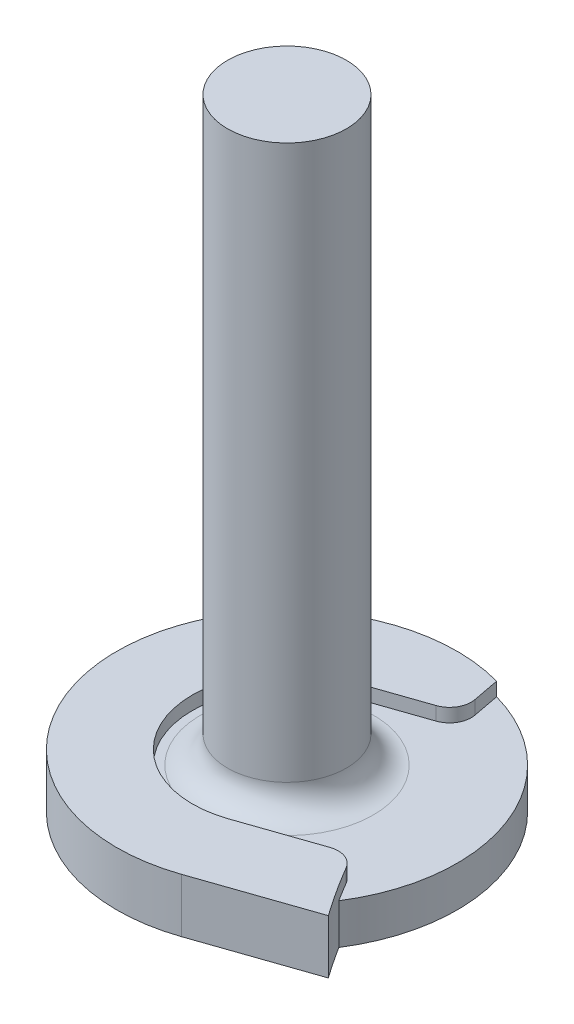
SolidWorks part; units mm, degrees
ref_plane "Alzado" through (0, 0, 0) normal (0, 0, 1) x (1, 0, 0)
ref_plane "Planta" through (0, 0, 0) normal (0, 1, 0) x (1, 0, 0)
ref_plane "Vista lateral" through (0, 0, 0) normal (1, 0, 0) x (0, 0, -1)
sketch "Croquis1" plane through (0, 0, 0) normal (0, 1, 0) x (1, 0, 0)
  line L4 (-28.127, 104.148) -> (-32.1677, 102.7551) construction
  line L5 (-28.127, 104.148) -> (-32.1677, 102.7551)
  arc A6 (-36.2739, 114.6672) -> (-32.1677, 102.7551) centre (-34.2208, 108.7112) ccw construction
  arc A7 (-28.9113, 105.3201) -> (-32.1677, 102.7551) centre (-34.2208, 108.7112) ccw
  arc A8 (-29.334, 106.0147) -> (-28.127, 104.148) centre (-7.0429, 119.104) ccw construction
  arc A9 (-28.9113, 105.3201) -> (-28.127, 104.148) centre (-7.0429, 119.104) ccw
extrude "Saliente-Extruir1" add sketch "Croquis1" along normal blind 1.5 contours A7 region at (-34.147, 0, -108.6415)
sketch "Sketch1" plane through (0, 1.5, 0) normal (0, 1, 0) x (1, 0, 0)
  circle A1 centre (-34.2208, 108.7112) radius 2.2
  dimension "D1" = 4.4
extrude "Boss-Extrude1" add sketch "Sketch1" along normal up to surface (21.5 mm away)
fillet "Fillet1" radius 1 1 edges at (-34.2208, 1.5, -106.5112)
sketch "Sketch2" plane through (0, 1.5, 0) normal (0, 1, 0) x (1, 0, 0)
  line L0 (-28.127, 104.148) -> (-32.1677, 102.7551) construction
  line L1 (-28.127, 104.148) -> (-32.1677, 102.7551)
  line L2 (-30.2846, 106.3659) -> (-33.0802, 105.4022) construction
  line L3 (-30.2846, 106.3659) -> (-33.0802, 105.4022)
  line L4 (-35.3614, 112.0201) -> (-32.8654, 112.8805) construction
  line L5 (-35.3614, 112.0201) -> (-32.8654, 112.8805)
  line L6 (-32.3431, 113.8009) -> (-32.5286, 114.7796)
  arc A0 (-28.9113, 105.3201) -> (-32.1677, 102.7551) centre (-34.2208, 108.7112) ccw construction
  arc A2 (-32.5286, 114.7796) -> (-32.1677, 102.7551) centre (-34.2208, 108.7112) ccw
  arc A4 (-30.9277, 128.9904) -> (-32.3431, 113.8009) centre (-7.0429, 119.104) ccw construction
  arc A5 (-35.3614, 112.0201) -> (-33.0802, 105.4022) centre (-34.2208, 108.7112) ccw construction
  arc A6 (-29.334, 106.0147) -> (-30.2846, 106.3659) centre (-30.0238, 105.6096) ccw construction
  arc A7 (-29.334, 106.0147) -> (-28.127, 104.148) centre (-7.0429, 119.104) ccw construction
  arc A8 (-35.3614, 112.0201) -> (-33.0802, 105.4022) centre (-34.2208, 108.7112) ccw
  arc A9 (-29.334, 106.0147) -> (-30.2846, 106.3659) centre (-30.0238, 105.6096) ccw
  arc A10 (-29.334, 106.0147) -> (-28.127, 104.148) centre (-7.0429, 119.104) ccw
  arc A11 (-32.8654, 112.8805) -> (-32.3431, 113.8009) centre (-33.1261, 113.6368) ccw construction
  arc A12 (-32.8654, 112.8805) -> (-32.3431, 113.8009) centre (-33.1261, 113.6368) ccw
extrude "Boss-Extrude2" add sketch "Sketch2" along normal blind 0.5
sketch "Sketch3" plane through (0, 0, 0) normal (0, -1, 0) x (1, 0, 0)
  line L1 (-36.7208, -111.2112) -> (-31.7208, -111.2112)
  line L2 (-36.7208, -111.2112) -> (-36.7208, -106.2112)
  line L3 (-36.7208, -106.2112) -> (-31.7208, -106.2112)
  line L4 (-31.7208, -111.2112) -> (-31.7208, -106.2112)
  line L5 (-36.7208, -111.2112) -> (-31.7208, -106.2112) construction
  line L6 (-36.7208, -106.2112) -> (-31.7208, -111.2112) construction
  arc A0 (-32.1677, -102.7551) -> (-28.9113, -105.3201) centre (-34.2208, -108.7112) ccw construction
  point P0 (-34.2208, -108.7112)
  dimension "D1" = 5
  dimension "D2" = 5
extrude "Cut-Extrude1" cut sketch "Sketch3" against normal blind 0.5 contours L4 L3 L2 L1
